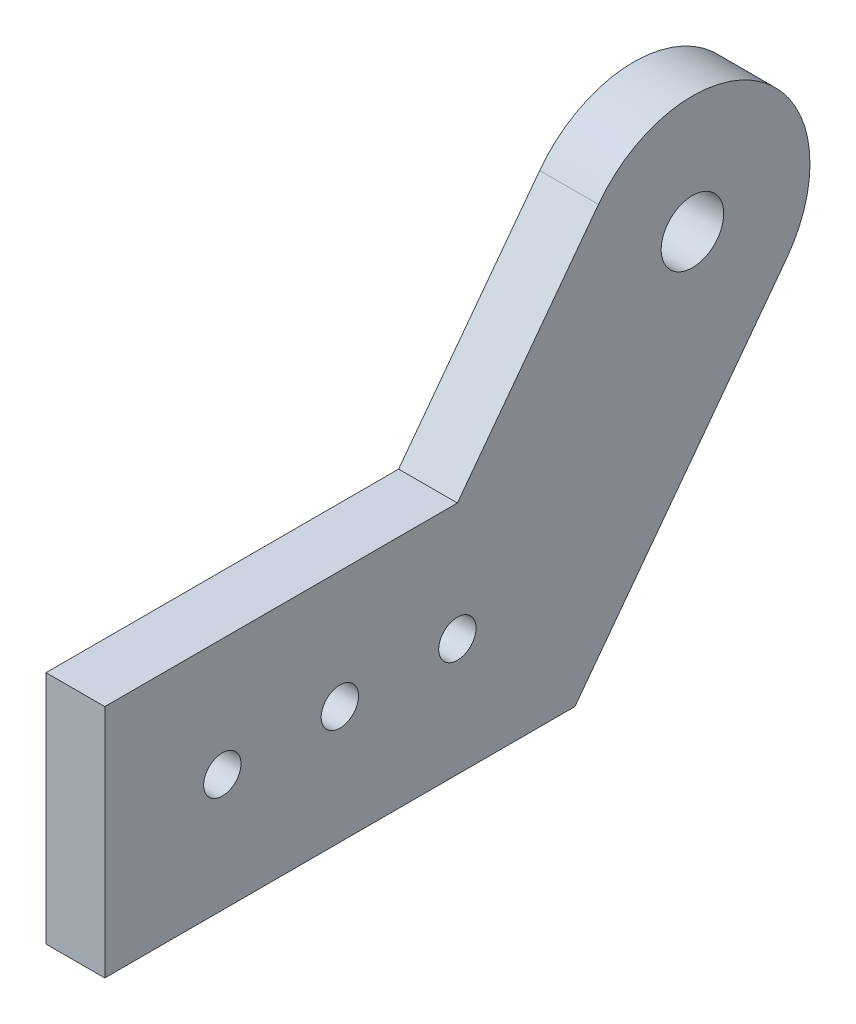
SolidWorks part; units mm, degrees
material "6061-T6 (SS)"
ref_plane "Front" through (0, 0, 0) normal (0, 0, 1) x (1, 0, 0)
ref_plane "Top" through (0, 0, 0) normal (0, 1, 0) x (1, 0, 0)
ref_plane "Right" through (0, 0, 0) normal (1, 0, 0) x (0, 0, -1)
sketch "Sketch1" plane through (0, 0, 0) normal (1, 0, 0) x (0, 0, -1)
  line L0 (50.8, 0) -> (73.66, 30.48)
  line L1 (0, 0) -> (50.8, 0)
  line L2 (0, 0) -> (0, 25.4)
  line L3 (0, 25.4) -> (38.1, 25.4)
  line L5 (53.34, 45.72) -> (38.1, 25.4)
  arc A0 (73.66, 30.48) -> (53.34, 45.72) centre (63.5, 38.1) ccw
  dimension "D3" = 63.5
  dimension "D1" = 25.4
  dimension "D2" = 25.4
  dimension "D4" = 50.8
  dimension "D5" = 38.1
extrude "Boss-Extrude1" add sketch "Sketch1" along normal blind 6.35
hole_wizard "#10-32 Tapped Hole1" positions "Sketch2" profile "Sketch3" tap size "#10-32" standard "ANSI Inch" end condition through all
sketch "Sketch2" plane through (6.35, 0, 0) normal (1, 0, 0) x (0, 0, -1)
  line L0 (0, 0) -> (12.7, 12.7) construction
  line L1 (12.7, 12.7) -> (25.4, 12.7) construction
  line L2 (25.4, 12.7) -> (38.1, 12.7) construction
  line L3 (38.1, 12.7) -> (50.8, 25.4) construction
  line L4 (38.1, 25.4) -> (0, 25.4) construction
  line L6 (0, 25.4) -> (0, 0) construction
  point P0 (12.7, 12.7)
  point P2 (25.4, 12.7)
  point P4 (38.1, 12.7)
  dimension "D1" = 50.8
  dimension "D2" = 12.7
sketch "Sketch3" plane through (6.35, 12.7, -12.7) normal (0, 1, 0) x (0, 0, -1)
  line L0 (0, 0) -> (0, 6.35)
  line L1 (0, 6.35) -> (2.0193, 6.35)
  line L2 (2.0193, 6.35) -> (2.0193, 0)
  line L5 (2.0193, 0) -> (0, 0)
  line L11 (0, -6.35) -> (0, 107.95) construction
  dimension "Thru Tap Drill Dia." = 4.0386
  dimension "Thru Tap Drill Depth" = 6.35
cosmetic thread "Hole Thread1"
cosmetic thread "Hole Thread2"
cosmetic thread "Hole Thread3"
hole_wizard "1/4 Clearance Hole1" positions "Sketch4" profile "Sketch5" hole size "1/4" standard "ANSI Inch" end condition through all
sketch "Sketch4" plane through (6.35, 0, 0) normal (1, 0, 0) x (0, 0, -1)
  arc A0 (73.66, 30.48) -> (53.34, 45.72) centre (63.5, 38.1) ccw construction
  point P0 (63.5, 38.1)
sketch "Sketch5" plane through (6.35, 38.1, -63.5) normal (0, 1, 0) x (0, 0, -1)
  line L0 (0, 0) -> (0, 6.35)
  line L1 (0, 6.35) -> (3.3782, 6.35)
  line L2 (3.3782, 6.35) -> (3.3782, 0)
  line L5 (3.3782, 0) -> (0, 0)
  line L11 (0, -6.35) -> (0, 107.95) construction
  dimension "Thru Hole Dia." = 6.7564
  dimension "Thru Hole Depth" = 6.35
